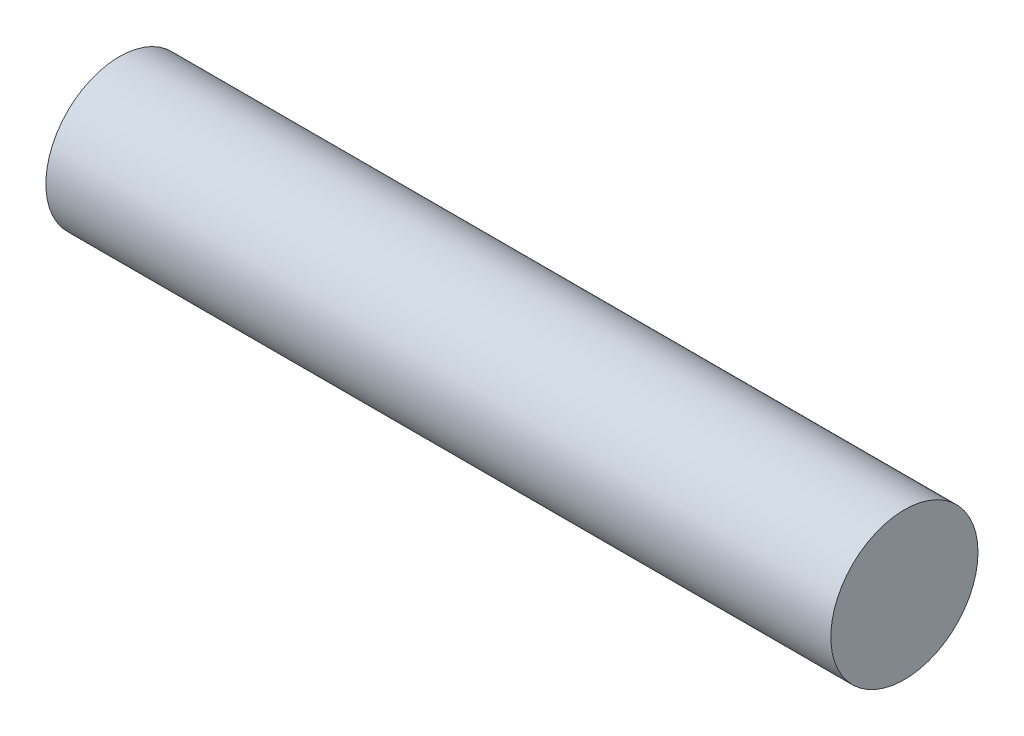
SolidWorks part; units mm, degrees
material "Простая углеродистая сталь"
ref_plane "Спереди" through (0, 0, 0) normal (0, 0, 1) x (1, 0, 0)
ref_plane "Сверху" through (0, 0, 0) normal (0, 1, 0) x (1, 0, 0)
ref_plane "Справа" through (0, 0, 0) normal (1, 0, 0) x (0, 0, -1)
sketch "Эскиз1" plane through (0, 0, 0) normal (1, 0, 0) x (0, 0, -1)
  circle A0 centre (0, 0) radius 3
  dimension "D1" = 6
extrude "Бобышка-Вытянуть1" add sketch "Эскиз1" along normal mid plane 32
